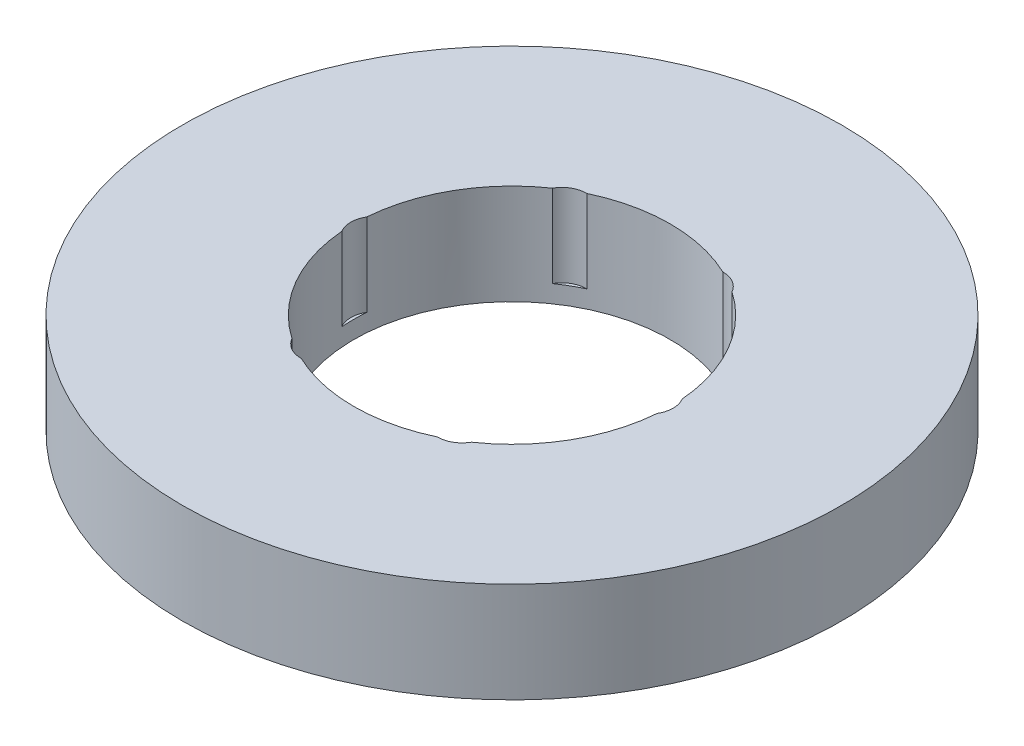
SolidWorks part; units mm, degrees
ref_plane "Front Plane" through (0, 0, 0) normal (0, 0, 1) x (1, 0, 0)
ref_plane "Top Plane" through (0, 0, 0) normal (0, 1, 0) x (1, 0, 0)
ref_plane "Right Plane" through (0, 0, 0) normal (1, 0, 0) x (0, 0, -1)
sketch "Sketch1" plane through (0, 0, 0) normal (0, 1, 0) x (1, 0, 0)
  circle A0 centre (0, 0) radius 62.5
  dimension "FLANGE_OD" = 125
extrude "Boss-Extrude1" add sketch "Sketch1" along normal blind 19
sketch "Sketch2" plane through (0, 0, 0) normal (0, 1, 0) x (1, 0, 0)
  circle A0 centre (0, 0) radius 30
  dimension "BORE_D" = 60
extrude "Cut-Extrude1" cut sketch "Sketch2" along normal through all
sketch "Sketch3" plane through (0, 19, 0) normal (0, 1, 0) x (1, 0, 0)
  circle A0 centre (0, 0) radius 25.9073 construction
  circle A1 centre (-25.9073, 0) radius 4.6528
  dimension "BOLT_D" = 9.3055
  dimension "BOLT_PCD" = 51.8146
extrude "Cut-Extrude2" cut sketch "Sketch3" against normal blind 15.6753
pattern_circular "CirPattern1" count 6 over 360 about axis through (0, 0, 0) along (0, 1, 0) of "Cut-Extrude2"
